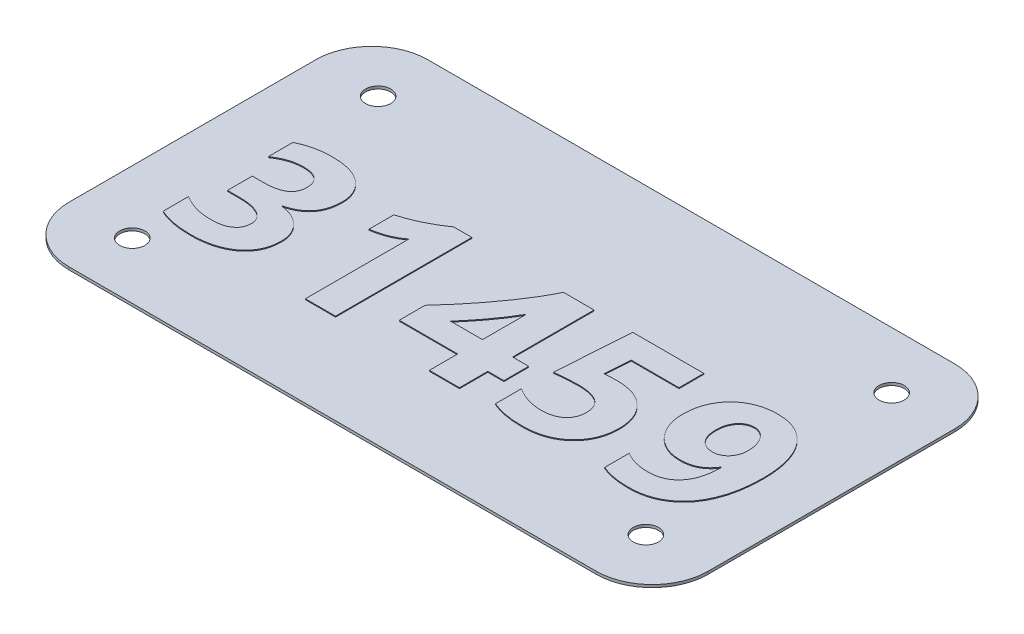
SolidWorks part; units mm, degrees
ref_plane "Front Plane" through (0, 0, 0) normal (0, 0, 1) x (1, 0, 0)
ref_plane "Top Plane" through (0, 0, 0) normal (0, 1, 0) x (1, 0, 0)
ref_plane "Right Plane" through (0, 0, 0) normal (1, 0, 0) x (0, 0, -1)
sketch "Sketch1" plane through (0, 0, 0) normal (0, 1, 0) x (1, 0, 0)
  line L1 (90.4875, -50.8) -> (-90.4875, -50.8)
  line L2 (90.4875, -50.8) -> (90.4875, 50.8)
  line L3 (90.4875, 50.8) -> (-90.4875, 50.8)
  line L4 (-90.4875, -50.8) -> (-90.4875, 50.8)
  line L5 (90.4875, -50.8) -> (-90.4875, 50.8) construction
  line L6 (90.4875, 50.8) -> (-90.4875, -50.8) construction
  point P0 (0, 0)
  dimension "D1" = 180.975
  dimension "D2" = 101.6
extrude "Boss-Extrude1" add sketch "Sketch1" along normal blind 0.762
hole_wizard "1/4 Clearance Hole1" positions "Sketch2" profile "Sketch3" hole size "1/4" standard "ANSI Inch" end condition through all
sketch "Sketch2" plane through (0, 0.762, 0) normal (0, 1, 0) x (1, 0, 0)
  line L1 (-90.4875, 50.8) -> (-90.4875, -50.8) construction
  line L2 (90.4875, 50.8) -> (-90.4875, 50.8) construction
  line L3 (90.4875, -50.8) -> (90.4875, 50.8) construction
  line L4 (-90.4875, -50.8) -> (90.4875, -50.8) construction
  point P0 (-72.7075, 34.798)
  point P4 (72.7075, 34.798)
  point P15 (-72.7075, -34.798)
  point P17 (72.7075, -34.798)
  point P22 (0, 0)
  point P23 (0, 0)
  point P24 (0, 0)
  dimension "D2" = 17.78
  dimension "D3" = 16.002
  dimension "D4" = 17.78
  dimension "D5" = 16.002
  dimension "D1" = 16.002
sketch "Sketch3" plane through (-72.7075, 0.762, -34.798) normal (1, 0, 0) x (0, 0, 1)
  line L0 (0, 0) -> (0, 0.762)
  line L1 (0, 0.762) -> (3.5712, 0.762)
  line L2 (3.5712, 0.762) -> (3.5712, 0)
  line L5 (3.5712, 0) -> (0, 0)
  line L11 (0, -6.35) -> (0, 107.95) construction
  dimension "Thru Hole Dia." = 7.1425
  dimension "Thru Hole Depth" = 0.762
fillet "Fillet1" radius 15.875 4 edges at (90.4875, 0.381, 50.8) (-90.4875, 0.381, 50.8) (90.4875, 0.381, -50.8) (-90.4875, 0.381, -50.8)
sketch "Sketch5" plane through (0, 0.762, 0) normal (0, 1, 0) x (1, 0, 0)
  line L0 (-90.4875, -25.4) -> (90.4875, -25.4) construction
  line L1 (-90.4875, 34.925) -> (-90.4875, -34.925) construction
  line L2 (90.4875, -34.925) -> (90.4875, 34.925) construction
  text T0 "31459" font "Ebrima" height 38.1
  dimension "D1" = 25.4
extrude "Boss-Extrude2" add sketch "Sketch5" along normal blind 0.254
equation "\"D4@Sketch2\"=\"D2@Sketch2\""
equation "\"D5@Sketch2\"=\"D3@Sketch2\""
equation "\"D1@Sketch2\"=\"D3@Sketch2\""
